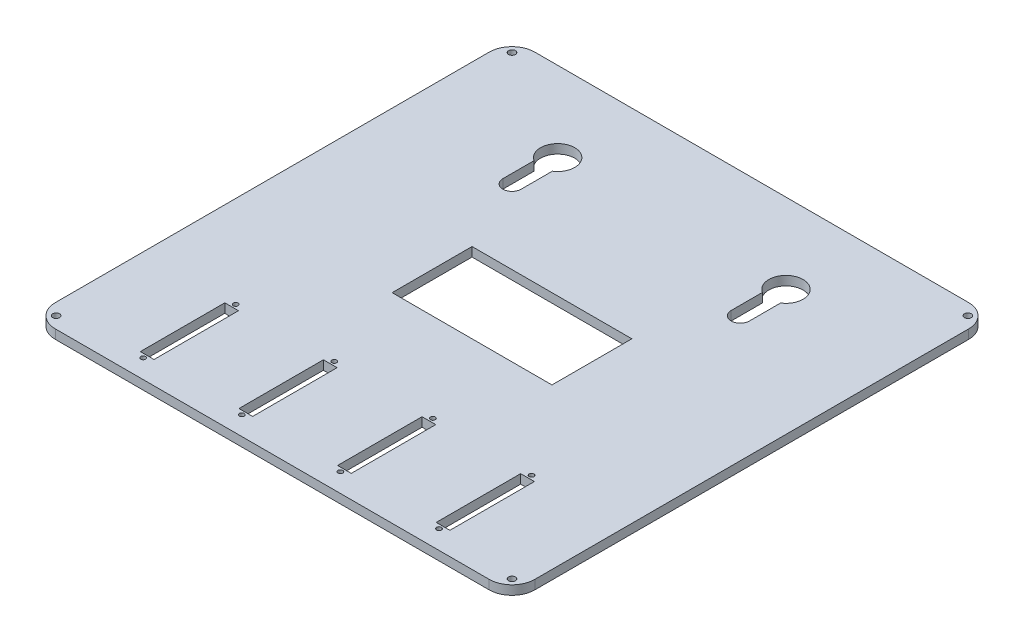
SolidWorks part; units mm, degrees
ref_plane "Front Plane" through (0, 0, 0) normal (0, 0, 1) x (1, 0, 0)
ref_plane "Top Plane" through (0, 0, 0) normal (0, 1, 0) x (1, 0, 0)
ref_plane "Right Plane" through (0, 0, 0) normal (1, 0, 0) x (0, 0, -1)
sketch "Sketch1" plane through (0, 0, 0) normal (0, 1, 0) x (1, 0, 0)
  line L0 (-101, -101) -> (-101, 101)
  line L5 (-105, -105) -> (105, -105)
  line L6 (-105, -105) -> (-105, 105)
  line L7 (-105, 105) -> (105, 105)
  line L8 (105, -105) -> (105, 105)
  line L9 (-101, 101) -> (101, 101)
  line L10 (101, -101) -> (101, 101)
  line L11 (-101, -101) -> (101, -101)
  line L12 (-101, 101) -> (-99.8333, 99.8333) construction
  line L13 (-55, 0) -> (55, 0) construction
  line L14 (-101, -101) -> (-99.8333, -99.8333) construction
  line L15 (0, -55) -> (0, 55) construction
  line L16 (101, -101) -> (99.8333, -99.8333) construction
  line L17 (101, 101) -> (99.8333, 99.8333) construction
  circle A1 centre (-99.8333, 99.8333) radius 1.5
  circle A2 centre (-99.8333, -99.8333) radius 1.5
  circle A3 centre (99.8333, -99.8333) radius 1.5
  circle A4 centre (99.8333, 99.8333) radius 1.5
  point P0 (0, 0)
  point P6 (-105, 0)
  point P7 (0, 105)
  dimension "D3" = 4
  dimension "D4" = 3
  dimension "D1" = 210
  dimension "D2" = 210
  dimension "D5" = 1.65
  dimension "D6" = 45
extrude "MainExtrude" add sketch "Sketch1" along normal mid plane 4 contours L6 L5 L8 L7
extrude "ScrewHoles" cut sketch "Sketch1<6>" along normal mid plane 4 contours A1 | A2 | A3 | A4
sketch "Sketch1<6>" plane through (0, 0, 0) normal (0, 1, 0) x (1, 0, 0) same geometry as "Sketch1"
fillet "RoundedCorners" radius 10 4 edges at (-105, 0, -105) (-105, 0, 105) (105, 0, -105) (105, 0, 105)
sketch "Sketch2" plane through (0, 2, 0) normal (0, 1, 0) x (1, 0, 0)
  line L0 (-50, 70) -> (-50, 50) construction
  line L1 (-67.8, -58) -> (-61.8, -58)
  line L2 (-67.8, -58) -> (-67.8, -95)
  line L3 (-67.8, -95) -> (-61.8, -95)
  line L4 (-61.8, -58) -> (-61.8, -95)
  line L5 (-24.6, -58) -> (-18.6, -58)
  line L6 (-24.6, -58) -> (-24.6, -95)
  line L7 (-24.6, -95) -> (-18.6, -95)
  line L8 (-18.6, -58) -> (-18.6, -95)
  line L9 (18.6, -58) -> (24.6, -58)
  line L10 (18.6, -58) -> (18.6, -95)
  line L11 (18.6, -95) -> (24.6, -95)
  line L12 (24.6, -58) -> (24.6, -95)
  line L13 (61.8, -58) -> (67.8, -58)
  line L14 (61.8, -58) -> (61.8, -95)
  line L15 (61.8, -95) -> (67.8, -95)
  line L16 (67.8, -58) -> (67.8, -95)
  line L17 (-95, -105) -> (95, -105) construction
  line L19 (-67.8, -58) -> (-105, -58) construction
  line L20 (-105, -95) -> (-105, 95) construction
  line L21 (-61.8, -58) -> (-24.6, -58) construction
  line L22 (-18.6, -58) -> (18.6, -58) construction
  line L23 (24.6, -58) -> (61.8, -58) construction
  line L25 (-105, 60) -> (-50, 60) construction
  line L26 (-95, 105) -> (95, 105) construction
  line L30 (-54, 50) -> (-54, 63.6557)
  line L31 (-46, 50) -> (-46, 63.6557)
  line L32 (0, -2.2) -> (0, 2.2) construction
  line L33 (46, 50) -> (46, 63.6557)
  line L34 (54, 50) -> (54, 63.6557)
  line L36 (35, -17.5) -> (-35, -17.5)
  line L37 (35, -17.5) -> (35, 17.5)
  line L38 (35, 17.5) -> (-35, 17.5)
  line L39 (-35, -17.5) -> (-35, 17.5)
  arc A0 (-54, 50) -> (-46, 50) centre (-50, 50) ccw
  arc A4 (-46, 63.6557) -> (-54, 63.6557) centre (-50, 70) ccw
  arc A5 (54, 50) -> (46, 50) centre (50, 50) cw
  arc A6 (46, 63.6557) -> (54, 63.6557) centre (50, 70) cw
  circle A7 centre (-64.8, -96.75) radius 1.05
  circle A8 centre (-64.8, -56.25) radius 1.05
  circle A9 centre (-21.6, -56.25) radius 1.05
  circle A10 centre (-21.6, -96.75) radius 1.05
  circle A11 centre (21.6, -56.25) radius 1.05
  circle A12 centre (21.6, -96.75) radius 1.05
  circle A13 centre (64.8, -56.25) radius 1.05
  circle A14 centre (64.8, -96.75) radius 1.05
  point P30 (0, 17.5)
  point P40 (-50, 60)
  point P42 (0, 0)
  point P48 (-35, 0)
  point P54 (-64.8, -95)
  point P58 (-61.8, -76.5)
  point P59 (-64.8, -58)
  point P60 (-21.6, -58)
  point P71 (-21.6, -95)
  dimension "D7" = 15
  dimension "D8" = 4
  dimension "D16" = 2.1
  dimension "D17" = 43.2
  dimension "D18" = 4
  dimension "D1" = 6
  dimension "D2" = 37
  dimension "D3" = 37.2
  dimension "D4" = 10
  dimension "D5" = 55
  dimension "D6" = 45
  dimension "D9" = 20
  dimension "D10" = 70
  dimension "D11" = 35
  dimension "D12" = 50
  dimension "D13" = 50
  dimension "D14" = 40.5
  dimension "D15" = 20.25
extrude "Knotches/Sliders" cut sketch "Sketch2" against normal up to surface (4 mm away) up to face at (-99.8333, -2, 98.3333)
sketch "Sketch6" plane through (71.6843, -2, 14.4809) normal (0, -1, 0) x (1, 0, 0)
  line L0 (-22.5243, 23.5191) -> (13.3157, 23.5191) construction
  line L1 (33.3157, 80.5191) -> (33.3157, -109.4809) construction
  line L2 (-9.8843, 43.5191) -> (-3.8843, 43.5191) construction
  circle A0 centre (-22.5243, 23.5191) radius 0.98
  circle A1 centre (-22.5243, 23.5191) radius 2
  circle A2 centre (13.3157, 23.5191) radius 2
  circle A3 centre (13.3157, 23.5191) radius 0.98
  circle A4 centre (-22.5243, -50.7509) radius 2
  circle A5 centre (-22.5243, -50.7509) radius 0.98
  circle A6 centre (13.3157, -50.7509) radius 0.98
  circle A7 centre (13.3157, -50.7509) radius 2
  dimension "D1" = 1.96
  dimension "D2" = 4
  dimension "D4" = 74.27
  dimension "D5" = 35.84
  dimension "D6" = 20
  dimension "D7" = 20
  dimension "D3" = 2
extrude "PCBHoles" add sketch "Sketch6" along normal blind 2
fillet "PCBRounds" radius 2 4 edges at (85, -2, -34.27) (49.16, -2, -34.27) (85, -2, 40) (49.16, -2, 40)
